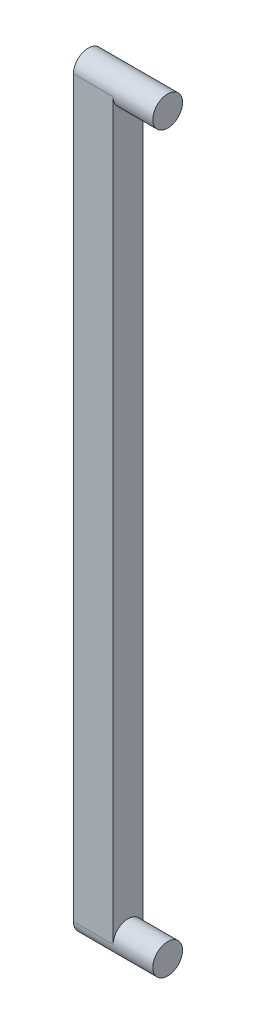
SolidWorks part; units mm, degrees
ref_plane "Front Plane" through (0, 0, 0) normal (1, 0, 0) x (0, 1, 0)
ref_plane "Top Plane" through (0, 0, 0) normal (0, 0, 1) x (0, 1, 0)
ref_plane "Right Plane" through (0, 0, 0) normal (0, 1, 0) x (-1, 0, 0)
sketch "Sketch1" plane through (0, 0, 0) normal (1, 0, 0) x (0, 1, 0)
  line L1 (0, 0) -> (37, 0)
  line L2 (0, 0) -> (0, 1.5)
  line L3 (0, 1.5) -> (37, 1.5)
  line L4 (37, 0) -> (37, 1.5)
  circle A0 centre (0, 0.75) radius 0.75
  circle A1 centre (37, 0.75) radius 0.75
  dimension "D2" = 1.5
  dimension "D1" = 37
extrude "Boss-Extrude1" add sketch "Sketch1" along normal blind 2 contours L2 A0 | L2 A0 | A1 L3 A0 L1 | L4 A1 | L4 A1 region at (0, 18.5, 0.75) region at (0, -0.3183, 0.75) region at (0, 0.3183, 0.75) region at (0, 36.6817, 0.75) region at (0, 37.3183, 0.75)
extrude "Boss-Extrude2" add sketch "Sketch1<3>" along normal blind 4 contours L4 A1 | L4 A1 | L2 A0 | L2 A0 region at (0, -0.3183, 0.75) region at (0, 0.3183, 0.75) region at (0, 36.6817, 0.75) region at (0, 37.3183, 0.75)
sketch "Sketch1<3>" plane through (0, 0, 0) normal (1, 0, 0) x (0, 1, 0) same geometry as "Sketch1"
